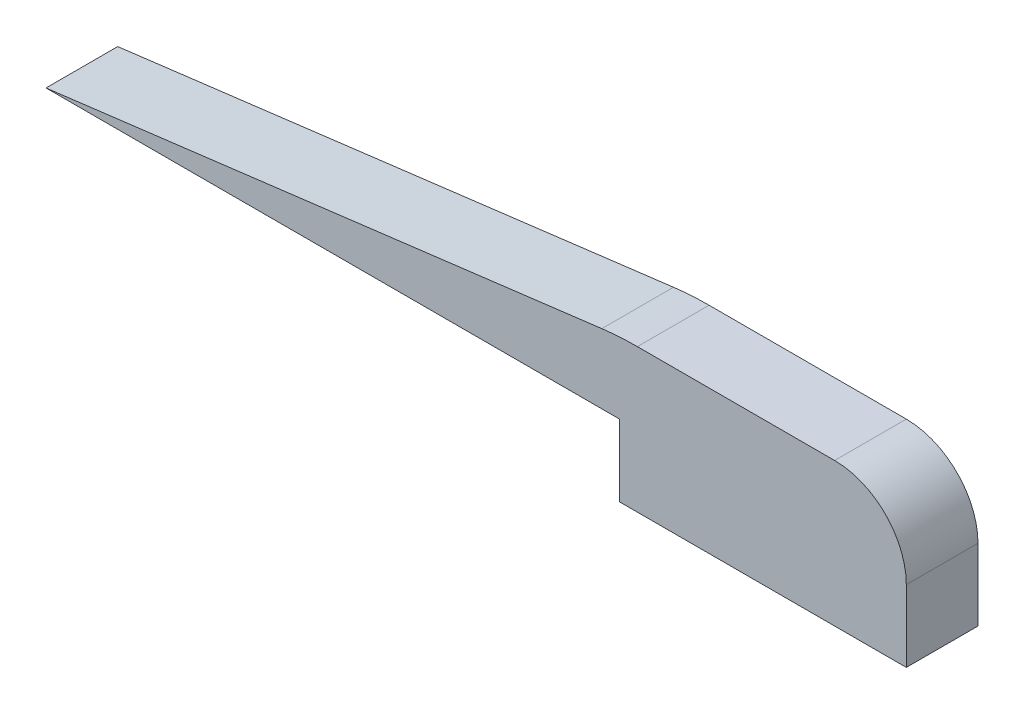
SolidWorks part; units mm, degrees
ref_plane "Front Plane" through (0, 0, 0) normal (0, 0, 1) x (1, 0, 0)
ref_plane "Top Plane" through (0, 0, 0) normal (0, 1, 0) x (1, 0, 0)
ref_plane "Right Plane" through (0, 0, 0) normal (1, 0, 0) x (0, 0, -1)
sketch "Sketch1" plane through (0, 0, 0) normal (0, 0, 1) x (1, 0, 0)
  line L0 (0, 0) -> (24.6154, 3.0769)
  line L1 (26.1907, 3.175) -> (34.925, 3.175)
  line L4 (38.1, -3.175) -> (25.4, -3.175)
  line L5 (25.4, -3.175) -> (25.4, 0)
  line L6 (25.4, 0) -> (0, 0)
  line L7 (38.1, 0) -> (38.1, -3.175)
  arc A0 (24.6154, 3.0769) -> (26.1907, 3.175) centre (26.1907, -9.525) cw
  arc A2 (34.925, 3.175) -> (38.1, 0) centre (34.925, 0) cw
  point P11 (25.4, 3.175)
  dimension "D1" = 12.7
  dimension "D2" = 3.175
  dimension "D6" = 3.175
  dimension "D3" = 25.4
  dimension "D4" = 3.175
  dimension "D5" = 12.7
extrude "Boss-Extrude1" add sketch "Sketch1" along normal blind 3.175
